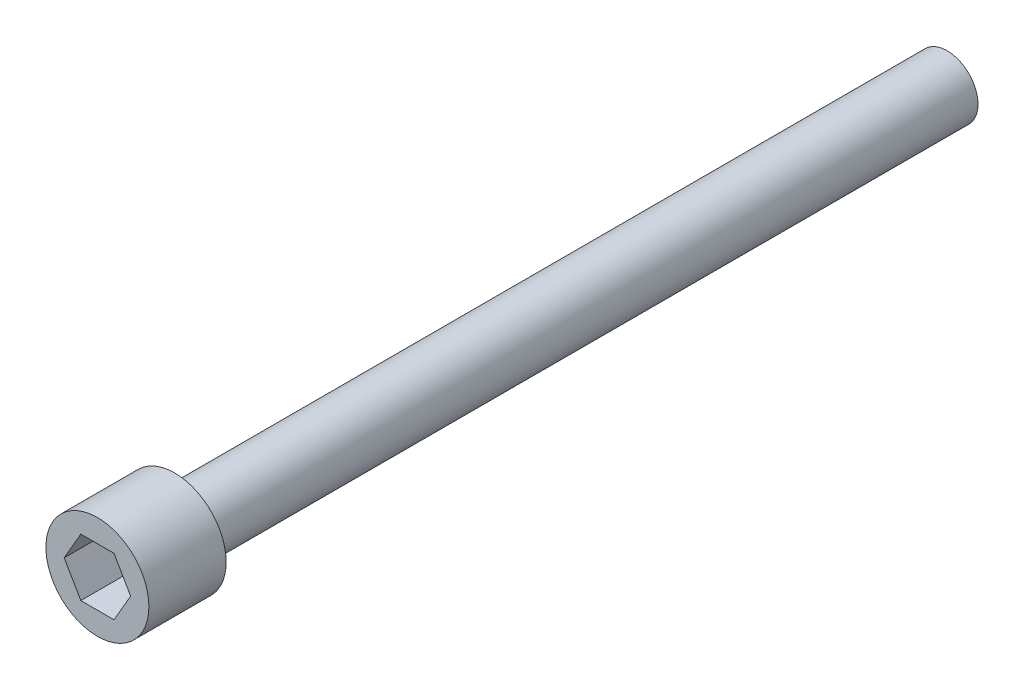
SolidWorks part; units mm, degrees
ref_plane "Front Plane" through (0, 0, 0) normal (0, 0, 1) x (1, 0, 0)
ref_plane "Top Plane" through (0, 0, 0) normal (0, 1, 0) x (1, 0, 0)
ref_plane "Right Plane" through (0, 0, 0) normal (1, 0, 0) x (0, 0, -1)
sketch "Sketch1" plane through (0, 0, 0) normal (0, 0, 1) x (1, 0, 0)
  circle A0 centre (-15, 15) radius 1.2
extrude "Boss-Extrude1" add sketch "Sketch1" against normal blind 30
sketch "Sketch2" plane through (0, 0, 0) normal (0, 0, 1) x (1, 0, 0)
  circle A0 centre (-15, 15) radius 2
extrude "Boss-Extrude2" add sketch "Sketch2" along normal blind 3
sketch "Sketch3" plane through (0, 0, 3) normal (0, 0, 1) x (1, 0, 0)
  line L1 (-13.7099, 15) -> (-14.355, 16.1172)
  line L2 (-14.355, 16.1172) -> (-15.645, 16.1172)
  line L3 (-15.645, 16.1172) -> (-16.2901, 15)
  line L4 (-16.2901, 15) -> (-15.645, 13.8828)
  line L5 (-15.645, 13.8828) -> (-14.355, 13.8828)
  line L6 (-14.355, 13.8828) -> (-13.7099, 15)
  circle A0 centre (-15, 15) radius 1.1172 construction
extrude "Cut-Extrude1" cut sketch "Sketch3" against normal blind 2
